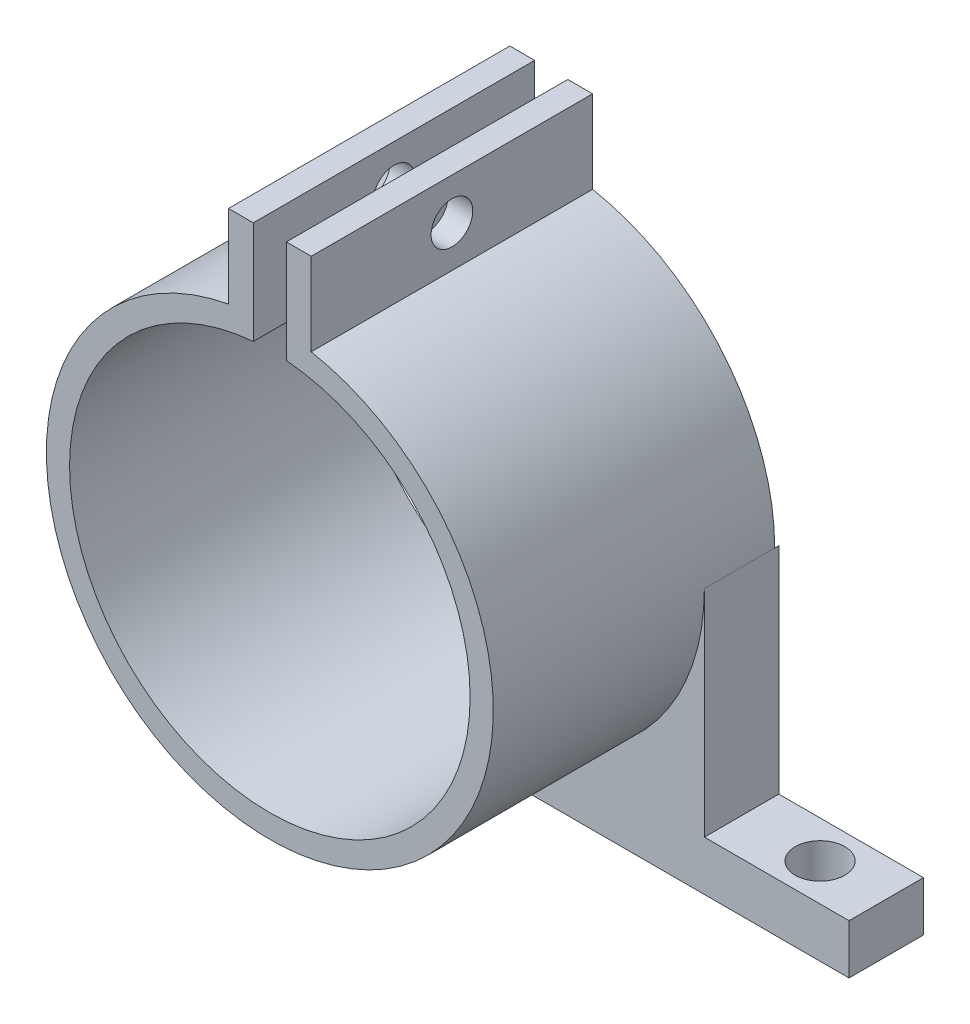
SolidWorks part; units mm, degrees
ref_plane "Front Plane" through (0, 0, 0) normal (0, 0, 1) x (1, 0, 0)
ref_plane "Top Plane" through (0, 0, 0) normal (0, 1, 0) x (1, 0, 0)
ref_plane "Right Plane" through (0, 0, 0) normal (1, 0, 0) x (0, 0, -1)
sketch "Sketch1" plane through (0, 0, 0) normal (0, 1, 0) x (1, 0, 0)
  line L0 (-55, 0) -> (55, 0) construction
  line L1 (-22.24, 2.25) -> (22.24, 2.25)
  line L2 (-22.24, 2.25) -> (-22.24, -2.25)
  line L3 (-22.24, -2.25) -> (22.24, -2.25)
  line L4 (22.24, 2.25) -> (22.24, -2.25)
  line L5 (-22.24, 2.25) -> (22.24, -2.25) construction
  line L6 (-22.24, -2.25) -> (22.24, 2.25) construction
  circle A0 centre (-18.24, 0) radius 1.5
  circle A1 centre (18.24, 0) radius 1.5
  point P0 (0, 0)
  dimension "D3" = 3
  dimension "D4" = 3
  dimension "D1" = 4.5
  dimension "D2" = 44.48
  dimension "D5" = 4
  dimension "D6" = 4
  dimension "D7" = 36.48
  dimension "D8" = 2.25
extrude "Boss-Extrude1" add sketch "Sketch1" along normal blind 3
sketch "Sketch2" plane through (0, 0, 0) normal (0, 0, 1) x (1, 0, 0)
  line L0 (0, -2.475) -> (0, 2.475) construction
  line L1 (-22.24, 3) -> (22.24, 3) construction
  line L6 (-13.5, 16) -> (-13.5, 3)
  line L7 (-13.5, 3) -> (-3.6401, 3)
  line L8 (13.5, 16) -> (13.5, 3)
  line L9 (13.5, 3) -> (3.6401, 3)
  line L10 (-2.5, 29.2665) -> (-2.5, 34.2665)
  line L11 (-2.5, 34.2665) -> (2.5, 34.2665)
  line L12 (2.5, 34.2665) -> (2.5, 29.2665)
  line L14 (-1, 37.2526) -> (1, 37.2526)
  line L15 (-1, 37.2526) -> (-1, 26.0338)
  line L16 (-1, 26.0338) -> (1, 26.0338)
  line L17 (1, 37.2526) -> (1, 26.0338)
  line L18 (-1, 37.2526) -> (1, 26.0338) construction
  line L19 (-1, 26.0338) -> (1, 37.2526) construction
  circle A0 centre (0, 16) radius 12.1
  circle A4 centre (0, 16) radius 13.5
  arc A5 (-13.5, 16) -> (-3.6401, 3) centre (0, 16) ccw
  arc A6 (3.6401, 3) -> (13.5, 16) centre (0, 16) ccw
  arc A7 (-2.5, 29.2665) -> (2.5, 29.2665) centre (0, 16) cw
  point P22 (0, 31.6432)
  dimension "D1" = 24.2
  dimension "D3" = 27
  dimension "D2" = 13
  dimension "D4" = 5
  dimension "D5" = 2.5
  dimension "D6" = 5
  dimension "D7" = 2
extrude "Boss-Extrude2" add sketch "Sketch2" along normal blind 15 and the other way blind 2 contours A4 L15 L11 L10 | A4 L12 L11 L17 | A4 L17 A0 L15 region at (-10.0986, 24.3733, 0) region at (-1.755, 31.8224, 0) region at (1.755, 31.8224, 0)
extrude "Boss-Extrude3" add sketch "Sketch2<3>" along normal mid plane 4.5 contours A4 L9 L8 | A4 L6 L7 region at (-10.9046, 5.9729, 0) region at (10.9046, 5.9729, 0)
sketch "Sketch2<3>" plane through (0, 0, 0) normal (0, 0, 1) x (1, 0, 0) same geometry as "Sketch2"
sketch "Sketch3" plane through (0, 0, 0) normal (1, 0, 0) x (0, 0, -1)
  line L0 (2, 34.2665) -> (2, 29.2665) construction
  line L1 (2, 29.2665) -> (-15, 29.2665) construction
  circle A0 centre (-6.5, 31.7665) radius 1.2587
  dimension "D1" = 8.5
  dimension "D2" = 2.5
extrude "Cut-Extrude1" cut sketch "Sketch3" against normal through all both and the other way through all
